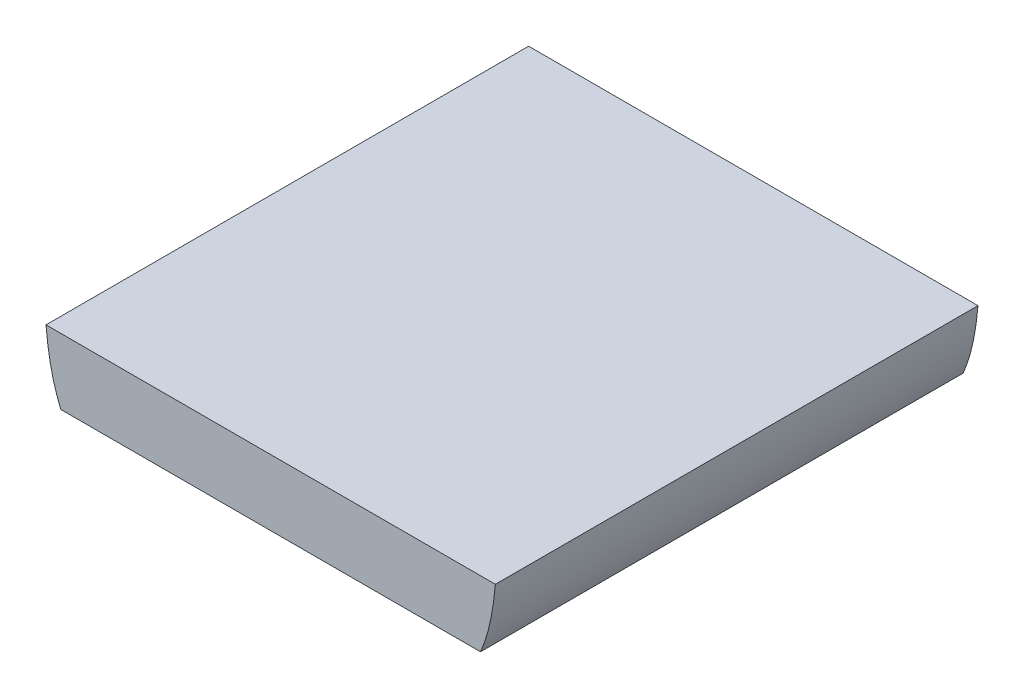
SolidWorks part; units mm, degrees
ref_plane "Front Plane" through (0, 0, 0) normal (0, 0, 1) x (1, 0, 0)
ref_plane "Top Plane" through (0, 0, 0) normal (0, 1, 0) x (1, 0, 0)
ref_plane "Right Plane" through (0, 0, 0) normal (1, 0, 0) x (0, 0, -1)
sketch "Sketch1" plane through (0, 0, 0) normal (0, 0, 1) x (1, 0, 0)
  line L0 (0, 0) -> (0, 222.758) construction
  line L2 (-342.9, 222.758) -> (342.9, 222.758)
  conic Q0 (342.9, 222.758) -> (0, 0) control (323.6021, 0) rho 0.570465
  conic Q1 (-342.9, 222.758) -> (0, 0) control (-323.6021, 0) rho 0.570465
extrude "Boss-Extrude1" add sketch "Sketch1" against normal blind 368.3 and the other way blind 368.3 contours Q1 Q0 L2
sketch "Sketch6" plane through (0, 0, 0) normal (1, 0, 0) x (0, 0, -1)
  line L0 (0, 0) -> (402.7895, 12.7)
  line L1 (0, 0) -> (0, 317.8845) construction
  line L2 (0, 0) -> (-402.7895, 12.7)
  dimension "D1" = 12.7
ref_plane "Plane1" through (304.8, 0, 0) normal (1, 0, 0) x (0, 0, -1)
ref_plane "Plane2" [suppressed] through (0, 0, 401.32) normal (0, 0, 1) x (1, 0, 0)
sketch "Sketch29" plane through (0, 0, 0) normal (1, 0, 0) x (0, 0, -1)
  line L0 (0, 7.9367) -> (74.9675, 7.9367)
  line L1 (74.9675, 7.9367) -> (308.7791, 142.4931)
  line L3 (308.7791, 142.4931) -> (642.4614, 142.4931)
  point P6 (0, -63.5)
sweep "Engine Line" [suppressed] add path "Sketch29" circular profile diameter 12.7 parameters "D3"=12.7
sketch "Sketch42" plane through (0, 0, 0) normal (0, 0, 1) x (1, 0, 0)
  circle A0 centre (0, 6.35) radius 6.35
extrude "Boss-Extrude2" [suppressed] add sketch "Sketch42" against normal blind 635
sketch "Sketch43" plane through (0, 0, -368.3) normal (0, 0, -1) x (-1, 0, 0)
  circle A0 centre (0, 209.4482) radius 6.35
extrude "Boss-Extrude3" [suppressed] add sketch "Sketch43" along normal blind 142.748
ref_plane "Plane4" through (0, 0, 381) normal (0, 0, 1) x (1, 0, 0)
sketch "Sketch41" plane through (0, 0, 381) normal (0, 0, 1) x (1, 0, 0)
  line L0 (-0.3885, -71.0751) -> (-0.3885, 316.4102) construction
  conic Q0 (-0.3885, -71.0751) -> (301.9685, 246.7379) control (301.9685, -71.1416) rho 0.504796
  conic Q1 (-0.3885, -71.0751) -> (-302.7456, 246.7379) control (-302.7456, -71.1416) rho 0.504796
ref_plane "Plane5" through (342.9, 0, 0) normal (1, 0, 0) x (0, 0, -1)
sketch "Sketch44" plane through (342.9, 0, 0) normal (1, 0, 0) x (0, 0, -1)
  circle A0 centre (-360.0842, 200.1725) radius 12.7
sketch "Sketch45" plane through (0, 0, 0) normal (0, 0, 1) x (1, 0, 0)
  line L0 (-363.6888, 122.174) -> (403.1456, 122.174)
  dimension "D1" = 100.584
split "Split1" trim tools "Sketch45" bodies to split 103 resulting bodies 127
